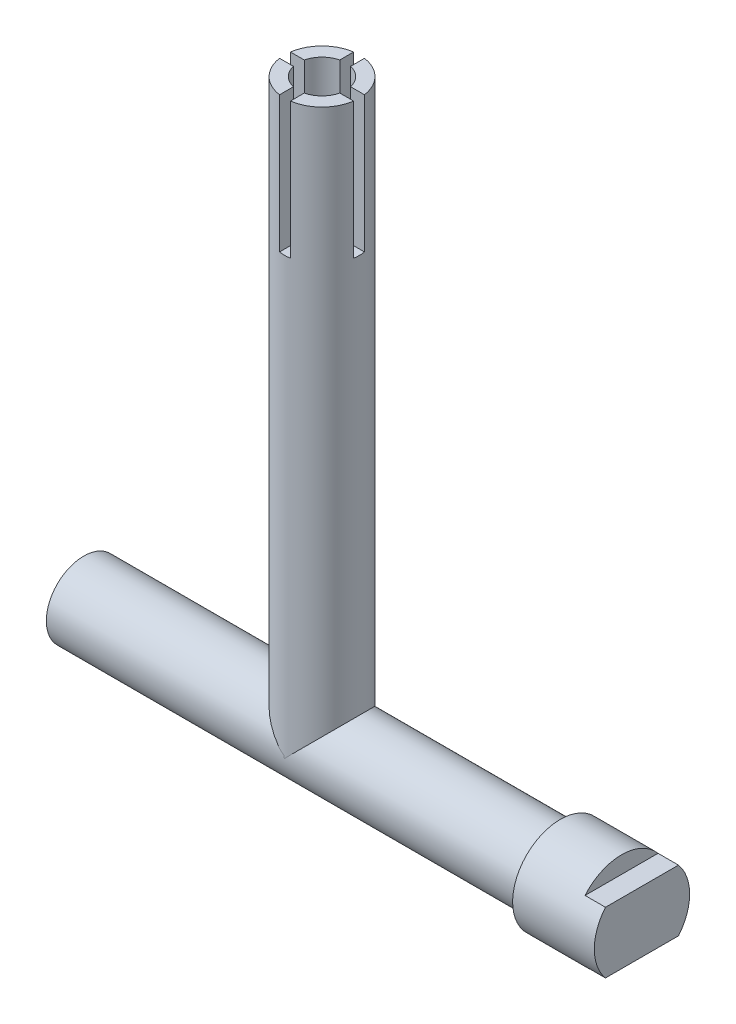
SolidWorks part; units mm, degrees
material "Сталь 10кп ГОСТ 535-88"
ref_plane "Спереди" through (0, 0, 0) normal (0, 0, 1) x (1, 0, 0)
ref_plane "Сверху" through (0, 0, 0) normal (0, 1, 0) x (1, 0, 0)
ref_plane "Справа" through (0, 0, 0) normal (1, 0, 0) x (0, 0, -1)
sketch "Эскиз1" plane through (0, 0, 0) normal (1, 0, 0) x (0, 0, -1)
  circle A0 centre (0, 0) radius 2.75
  dimension "D1" = 5.5
extrude "Бобышка-Вытянуть1" add sketch "Эскиз1" along normal blind 35
sketch "Эскиз2" plane through (0, 0, 0) normal (0, 1, 0) x (1, 0, 0)
  line L0 (0, 0) -> (35, 0) construction
  line L1 (35, -2.75) -> (35, 2.75) construction
  circle A0 centre (17.5, 0) radius 2.75
  dimension "D1" = 5.5
extrude "Бобышка-Вытянуть2" add sketch "Эскиз2" along normal blind 42 separate body
hole_wizard "Диаметр отверстия Ø3.5 (3.5)1" positions "Трехмерный эскиз1" profile "Эскиз3" hole size "Ø3.5" standard "Ansi Metric"
sketch3d "Трехмерный эскиз1"
  line L0 (17.5, 42, 0) -> (17.5, 0, 0) construction
  point P0 (17.5, 42, 0)
sketch "Эскиз3" plane through (17.5, 42, 0) normal (1, 0, 0) x (0, 0, 1)
  line L0 (0, 0) -> (0, 14.0515)
  line L1 (0, 14.0515) -> (1.75, 13)
  line L2 (1.75, 13) -> (1.75, 0)
  line L5 (1.75, 0) -> (0, 0)
  line L10 (0, 14.0515) -> (-1.75, 13) construction
  line L11 (0, -6.35) -> (0, 107.95) construction
  dimension "Диаметр отверстия" = 3.5
  dimension "Глубина отверстия" = 13
  dimension "Угол заточки сверла" = 118
sketch "Эскиз4" plane through (0, 42, 0) normal (0, 1, 0) x (1, 0, 0)
  line L1 (17.1, -4) -> (17.9, -4)
  line L2 (17.1, -4) -> (17.1, 4)
  line L3 (17.1, 4) -> (17.9, 4)
  line L4 (17.9, -4) -> (17.9, 4)
  line L5 (17.1, -4) -> (17.9, 4) construction
  line L6 (17.1, 4) -> (17.9, -4) construction
  line L7 (13.5, -0.4) -> (21.5, -0.4)
  line L8 (13.5, -0.4) -> (13.5, 0.4)
  line L9 (13.5, 0.4) -> (21.5, 0.4)
  line L10 (21.5, -0.4) -> (21.5, 0.4)
  line L11 (13.5, -0.4) -> (21.5, 0.4) construction
  line L12 (13.5, 0.4) -> (21.5, -0.4) construction
  point P0 (17.5, 0)
  point P6 (17.5, 0)
  circle M1 centre (17.5, 0) radius 1.75
  circle M2 centre (17.5, 0) radius 2.75
  dimension "D1" = 0.8
  dimension "D2" = 8
extrude "Вырез-Вытянуть1" cut sketch "Эскиз4" against normal blind 10 contours L4 L3 L2 M2 | L4 L2 M1 M2 | L2 L9 L4 M1 | L9 L2 L7 L4 | L9 L7 L2 M1 | L9 L7 M2 M1 | L9 L8 L7 M2 | L4 L2 M2 M1 | L7 L2 L4 M1 | L1 L4 L2 M2 | L9 L4 L7 M1 | L9 L7 M1 M2 | L7 L10 L9 M2 region at (17.5, 42, 3.3701) region at (17.5, 42, 2.2374) region at (17.5, 42, 1.0674) region at (15.2626, 42, 0) region at (14.1299, 42, 0) region at (20.8701, 42, 0) region at (19.7374, 42, 0) region at (16.4326, 42, 0) region at (17.5, 42, 0) region at (18.5674, 42, 0) region at (17.5, 42, -1.0674) region at (17.5, 42, -2.2374) region at (17.5, 42, -3.3701)
sketch "Эскиз5" plane through (35, 0, 0) normal (1, 0, 0) x (0, 0, -1)
  circle A0 centre (0, 0) radius 3.5
  dimension "D1" = 7
extrude "Бобышка-Вытянуть3" add sketch "Эскиз5" along normal blind 6
sketch "Эскиз6" plane through (41, 0, 0) normal (1, 0, 0) x (0, 0, -1)
  line L1 (-2.681, -2.25) -> (2.681, -2.25)
  line L2 (-2.681, -2.25) -> (-2.681, 2.25)
  line L3 (-2.681, 2.25) -> (2.681, 2.25)
  line L4 (2.681, -2.25) -> (2.681, 2.25)
  line L5 (-2.681, -2.25) -> (2.681, 2.25) construction
  line L6 (-2.681, 2.25) -> (2.681, -2.25) construction
  circle A0 centre (0, 0) radius 3.5 construction
  circle A1 centre (0, 0) radius 3.5
  circle M1 centre (0, 0) radius 3.5
  dimension "D1" = 4.5
extrude "Вырез-Вытянуть2" cut sketch "Эскиз6" against normal blind 1.5 contours L3 M1 | L1 M1 region at (41, -2.7585, 0) region at (41, 2.7585, 0)
sketch "Эскиз7" plane through (0, 0, 0) normal (-1, 0, 0) x (0, 0, 1)
  circle A0 centre (0, 0) radius 2
  dimension "D1" = 4
extrude "Вырез-Вытянуть3" cut sketch "Эскиз7" against normal blind 7
hole_wizard "Отверстие обработанное метчиком M2.5x0.451" positions "Трехмерный эскиз2" profile "Эскиз8" tap size "M2.5x0.45" standard "Ansi Metric"
sketch3d "Трехмерный эскиз2"
  line L0 (7, 0, 0) -> (0, 0, 0) construction
  point P0 (7, 0, 0)
sketch "Эскиз8" plane through (7, 0, 0) normal (0, 1, 0) x (0, 0, 1)
  line L0 (0, 0) -> (0, 6.6159)
  line L1 (0, 6.6159) -> (1.025, 6)
  line L2 (1.025, 6) -> (1.025, 0)
  line L5 (1.025, 0) -> (0, 0)
  line L10 (0, 6.6159) -> (-1.025, 6) construction
  line L11 (0, -6.35) -> (0, 107.95) construction
  dimension "Диаметр сверла" = 2.05
  dimension "Глубина сверла" = 6
  dimension "Угол заточки сверла" = 118
cosmetic thread "Отверстие резьбы1" parameters "D1"=4.5, "D2"=2.5
split "Разделить1" bodies to split 108 resulting bodies 113 114 split by face at (35, 0, -2.75)
delete or keep bodies "Тело-Удалить/Сохранить 1" type delete bodies bodies 114
